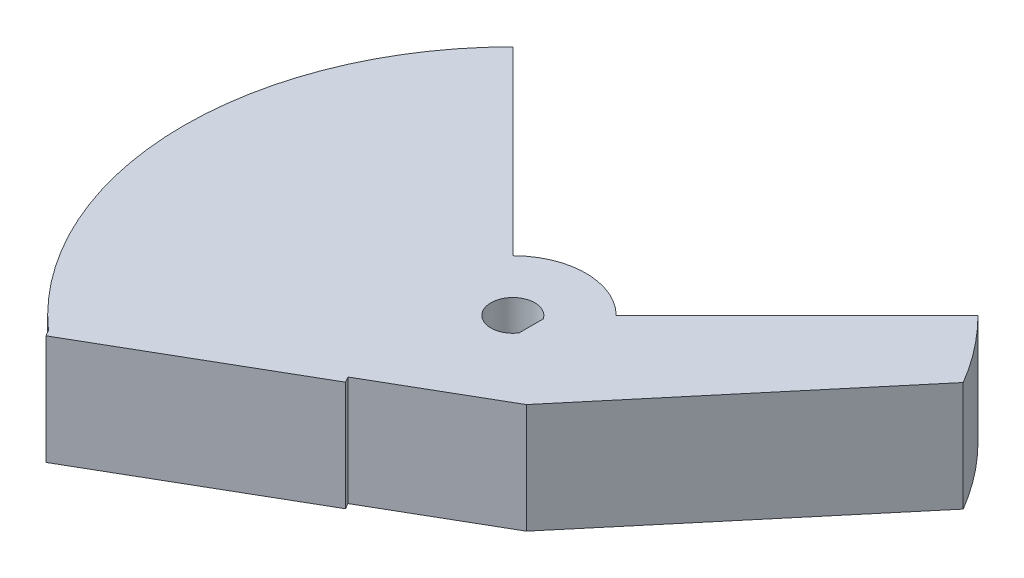
SolidWorks part; units mm, degrees
material "ABS"
ref_plane "Front Plane" through (0, 0, 0) normal (0, 0, 1) x (1, 0, 0)
ref_plane "Top Plane" through (0, 0, 0) normal (0, 1, 0) x (1, 0, 0)
ref_plane "Right Plane" through (0, 0, 0) normal (1, 0, 0) x (0, 0, -1)
sketch "Sketch1" plane through (0, 0, 0) normal (0, 1, 0) x (1, 0, 0)
  line L0 (-31.8198, 31.8198) -> (-7.0711, 7.0711)
  line L1 (7.0711, 7.0711) -> (31.8198, 31.8198)
  line L2 (0, 0) -> (0, 20) construction
  line L3 (0, 0) -> (-7.0711, 7.0711) construction
  line L4 (7.0711, 7.0711) -> (0, 0) construction
  arc A0 (-31.8198, 31.8198) -> (31.8198, 31.8198) centre (0, 0) ccw
  circle A1 centre (0, 0) radius 3
  arc A2 (7.0711, 7.0711) -> (-7.0711, 7.0711) centre (0, 0) ccw
  dimension "D1" = 6
  dimension "D2" = 90
  dimension "D3" = 20
  dimension "D4" = 45
extrude "Boss-Extrude1" add sketch "Sketch1" along normal blind 15
sketch "Sketch2" plane through (0, 15, 0) normal (0, 1, 0) x (1, 0, 0)
  line L0 (2.5, 1.6583) -> (2.5, -1.6583)
  line L1 (-3, 0) -> (-3, -6.6376) construction
  arc A0 (2.5, -1.6583) -> (2.5, 1.6583) centre (0, 0) ccw
  circle A1 centre (0, 0) radius 3 construction
  dimension "D1" = 5.5
extrude "Shaft D" add sketch "Sketch2" against normal up to surface (15 mm away) up to face at (0, 0, -0.9727)
sketch "Sketch3" plane through (0, 15, 0) normal (0, 1, 0) x (1, 0, 0)
  line L0 (-31.8198, 31.8198) -> (-27.5772, 36.0624)
  line L1 (-27.5772, 36.0624) -> (-27.5772, 27.5772)
  line L2 (-7.0711, 7.0711) -> (-31.8198, 31.8198) construction
  line L3 (-27.5772, 27.5772) -> (-31.8198, 31.8198)
  line L4 (0, 0) -> (0, 30.6174) construction
  line L5 (27.5772, 27.5772) -> (31.8198, 31.8198)
  line L6 (27.5772, 36.0624) -> (27.5772, 27.5772)
  line L7 (31.8198, 31.8198) -> (27.5772, 36.0624)
  dimension "D1" = 6
extrude "Boss-Extrude2" [suppressed] add sketch "Sketch3" against normal up to surface (15 mm away) up to face at (0, 0, -0.9727)
sketch "Sketch5" plane through (0, 15, 0) normal (0, 1, 0) x (1, 0, 0)
  line L0 (31.8198, 31.8198) -> (0, 0) construction
  line L1 (0, 0) -> (-31.8198, 31.8198) construction
  line L2 (-31.8198, 31.8198) -> (31.8198, 31.8198) construction
sketch "Sketch4" plane through (0, 15, 0) normal (0, 1, 0) x (1, 0, 0)
  line L0 (-148.943, 0) -> (142.5774, 0) construction
  line L1 (0, 0) -> (-107.5774, -62.1099) construction
  line L2 (0, 0) -> (96.6052, -81.0614) construction
  line L8 (0, 0) -> (81.0614, 96.6052) construction
  line L9 (0, 0) -> (62.1099, -107.5774) construction
  line L10 (-107.5774, -62.1099) -> (62.1099, -107.5774) construction
  line L11 (81.0614, 96.6052) -> (96.6052, -81.0614) construction
  line L14 (11.4907, -9.6418) -> (45.5038, 30.8934)
  line L15 (11.4907, -9.6418) -> (-38.9929, -38.7885)
  arc A2 (-38.9929, -38.7885) -> (45.5038, 30.8934) centre (0, 0) ccw
  dimension "D4" = 55
  dimension "D1" = 40
  dimension "D3" = 30
  dimension "D5" = 15
extrude "Cut-Extrude1" cut sketch "Sketch4" against normal through all
sketch "Sketch6" plane through (7.0477, 0, 12.207) normal (0.5, 0, 0.866) x (0.866, 0, -0.5)
  line L0 (5.1303, 0) -> (-42.7355, 0) construction
  line L1 (-42.7355, 15) -> (-12.7355, 15)
  line L2 (-42.7355, 15) -> (-42.7355, 0)
  line L3 (-42.7355, 0) -> (-12.7355, 0)
  line L4 (-12.7355, 15) -> (-12.7355, 0)
  line L5 (-42.7355, 15) -> (-12.7355, 0) construction
  line L6 (-42.7355, 0) -> (-12.7355, 15) construction
  point P4 (-27.7355, 7.5)
  dimension "D1" = 30
extrude "Boss-Extrude3" add sketch "Sketch6" along normal blind 0.9
